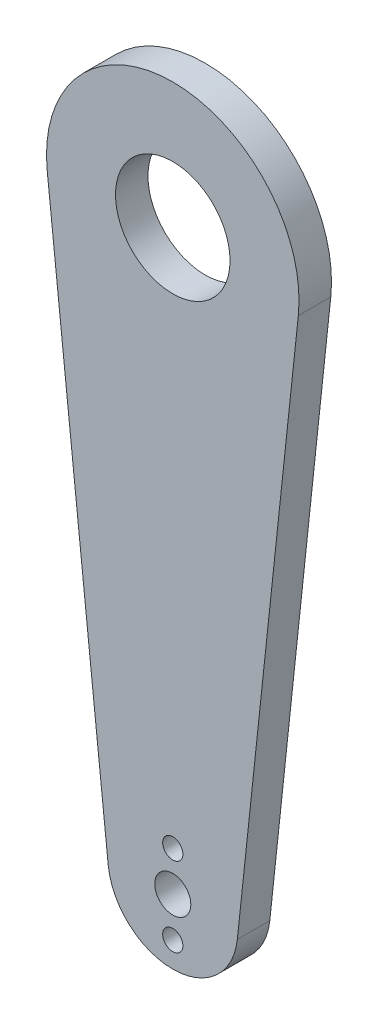
SolidWorks part; units mm, degrees
ref_plane "Front Plane" through (0, 0, 0) normal (0, 0, 1) x (1, 0, 0)
ref_plane "Top Plane" through (0, 0, 0) normal (0, 1, 0) x (1, 0, 0)
ref_plane "Right Plane" through (0, 0, 0) normal (1, 0, 0) x (0, 0, -1)
ref_axis "X Axis" through (-88.99, 0, 0) along (1, 0, 0)
ref_axis "Y Axiz" through (0, 0, 55) along (0, 0, -1)
ref_axis "Z Axis" through (0, 55, 0) along (0, -1, 0)
sketch "Sketch1" plane through (0, 0, 0) normal (0, 0, 1) x (1, 0, 0)
  line L1 (-8.9491, -0.9563) -> (-17.4009, 78.1406)
  line L3 (0, -5.5) -> (0, 5.5) construction
  line L4 (17.4009, 78.1406) -> (8.9491, -0.9563)
  line L5 (0, 0) -> (0, 80) construction
  arc A1 (-8.9491, -0.9563) -> (8.9491, -0.9563) centre (0, 0) ccw
  circle A2 centre (0, 80) radius 7.9375
  arc A3 (17.4009, 78.1406) -> (-17.4009, 78.1406) centre (0, 80) ccw
  circle A5 centre (0, 0) radius 2.5
  circle A6 centre (0, 5.5) radius 1.4
  circle A7 centre (0, -5.5) radius 1.4
  point P7 (0, 0)
  dimension "D1" = 5
  dimension "D3" = 18
  dimension "D4" = 15.875
  dimension "D5" = 35
  dimension "D2" = 2.8
  dimension "D6" = 80
  dimension "D7" = 5.5
extrude "Boss-Extrude1" add sketch "Sketch1" along normal blind 4.5
